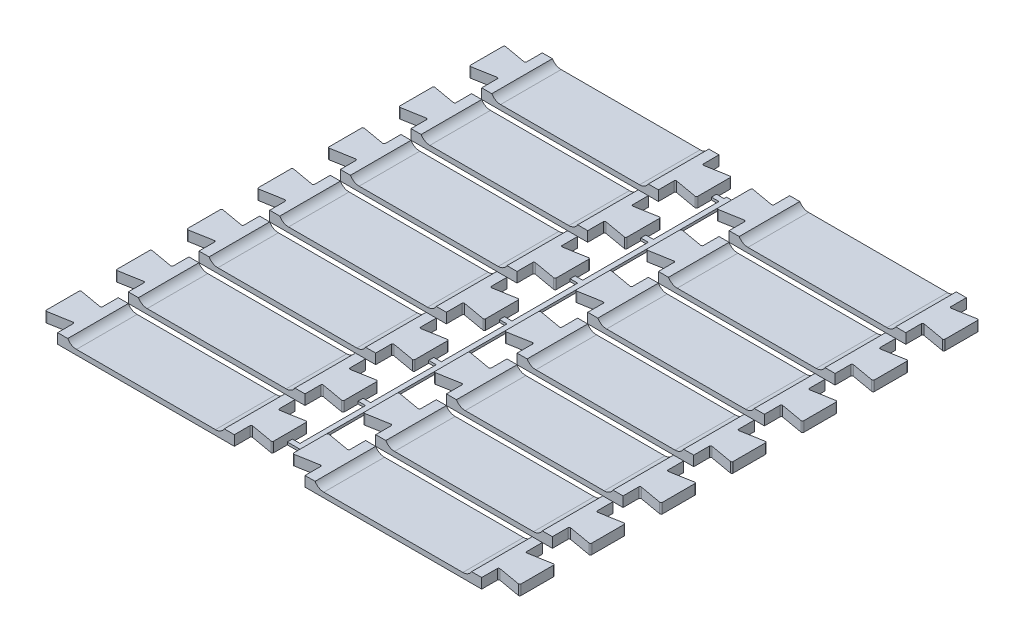
SolidWorks part; units mm, degrees
ref_plane "Front Plane" through (0, 0, 0) normal (0, 0, 1) x (1, 0, 0)
ref_plane "Top Plane" through (0, 0, 0) normal (0, 1, 0) x (1, 0, 0)
ref_plane "Right Plane" through (0, 0, 0) normal (1, 0, 0) x (0, 0, -1)
sketch "Sketch1" plane through (0, 0, 0) normal (0, 1, 0) x (1, 0, 0)
  line L0 (-17.5, 2.6184) -> (-22.5, 3.5)
  line L1 (-17.5, -6) -> (17.5, -6)
  line L2 (-17.5, -6) -> (-17.5, -2.6184)
  line L3 (-17.5, 6) -> (17.5, 6)
  line L4 (17.5, -6) -> (17.5, -2.6184)
  line L5 (-17.5, -6) -> (17.5, 6) construction
  line L6 (-17.5, 6) -> (17.5, -6) construction
  line L7 (-22.5, 3.5) -> (-22.5, -3.5)
  line L8 (-10, 0) -> (-18.3718, 0) construction
  line L9 (-17.5, -2.6184) -> (-22.5, -3.5)
  line L10 (-17.5, 2.6184) -> (-17.5, 6)
  line L11 (0, 0) -> (0, 6) construction
  line L12 (17.5, -2.6184) -> (22.5, -3.5)
  line L13 (22.5, 3.5) -> (22.5, -3.5)
  line L14 (17.5, 2.6184) -> (22.5, 3.5)
  line L15 (17.5, 2.6184) -> (17.5, 6)
  line L16 (-17.5, 6) -> (-27.9194, 6) construction
  point P0 (0, 0)
  point P13 (-22.5, 0)
  dimension "D1" = 12
  dimension "D2" = 35
  dimension "D3" = 3.5
  dimension "D4" = 80
  dimension "D5" = 5
extrude "Boss-Extrude1" add sketch "Sketch1" along normal blind 2
fillet "Fillet1" radius 0.25 8 edges at (-17.5, 1, 2.6184) (-22.5, 1, 3.5) (-22.5, 1, -3.5) (-17.5, 1, -2.6184) (17.5, 1, -2.6184) (22.5, 1, -3.5) (22.5, 1, 3.5) (17.5, 1, 2.6184)
shell "Shell1" [suppressed] thickness 1
fillet "Fillet2" [suppressed] radius 0.5
fillet "Fillet5" [suppressed] radius 1.5
sketch "Sketch2" plane through (0, 0, 0) normal (0, 0, 1) x (1, 0, 0)
  line L0 (-17.5, 2) -> (17.5, 2) construction
  line L1 (0, 0) -> (0, 2) construction
  line L2 (-14.5, 2) -> (-14.5, 5.1779)
  line L3 (-17.5, 0) -> (17.5, 0) construction
  line L4 (-14.5, 5.1779) -> (14.5, 5.1779)
  line L5 (14.5, 2) -> (14.5, 5.1779)
  spline S0 degree 3 poles (-14.5, 2) (-10.1117, 3.708) (-5.6899, 1.0248) (0, 1) knots 0 0 0 0 1 1 1 1
  spline S1 degree 3 poles (14.5, 2) (10.1117, 3.708) (5.6899, 1.0248) (0, 1) knots 0 0 0 0 1 1 1 1
  point P15 (0, 5.1779)
  dimension "D1" = 14.5
  dimension "D2" = 10
  dimension "D3" = 1
extrude "Cut-Extrude1" [suppressed] cut sketch "Sketch2" against normal mid plane 12
sketch "Sketch3" plane through (0, 2, 0) normal (0, 1, 0) x (1, 0, 0)
  line L0 (17.5, 6) -> (-17.5, 6) construction
  line L1 (-15.5, 6) -> (15.5, 6)
  line L2 (-15.5, 6) -> (-15.5, -6)
  line L3 (-15.5, -6) -> (15.5, -6)
  line L4 (15.5, 6) -> (15.5, -6)
  line L5 (-17.5, -6) -> (17.5, -6) construction
  line L6 (-17.5, 6) -> (-17.5, 2.9163) construction
  line L7 (17.5, 2.9163) -> (17.5, 6) construction
  point P8 (-17.5, 4.4582)
  point P11 (17.5, 4.4582)
  dimension "D1" = 2
  dimension "D2" = 2
extrude "Cut-Extrude2" cut sketch "Sketch3" against normal blind 1
fillet "Fillet6" radius 2 2 edges at (-15.5, 1, 0) (15.5, 1, 0)
sketch "Sketch4" plane through (0, 0, 0) normal (0, 1, 0) x (1, 0, 0)
  line L1 (-29.6701, -11.4809) -> (80.3299, -11.4809)
  line L2 (-29.6701, -11.4809) -> (-29.6701, 78.5191)
  line L3 (-29.6701, 78.5191) -> (80.3299, 78.5191)
  line L4 (80.3299, -11.4809) -> (80.3299, 78.5191)
  line L5 (21.5, 0.5) -> (24.5, 0.5)
  line L6 (21.5, 0.5) -> (21.5, -0.5)
  line L7 (21.5, -0.5) -> (24.5, -0.5)
  line L8 (24.5, 0.5) -> (24.5, -0.5)
  dimension "D1" = 90
  dimension "D2" = 110
  dimension "D3" = 3
  dimension "D4" = 21.5
  dimension "D5" = 0.5
  dimension "D6" = 1
extrude "Boss-Extrude2" add sketch "Sketch4" along normal blind 0.5 contours L7 L8 L5 L6
ref_plane "Plane1" through (24.5, 0, 0) normal (1, 0, 0) x (0, 0, -1)
mirror "Mirror1" about plane through (24.5, 0, 0) normal (1, 0, 0) of bodies 104
sketch "Sketch6" plane through (0, 0, 0) normal (0, 1, 0) x (1, 0, 0)
  line L0 (24.5, 0) -> (24.5, 45.0914) construction
  line L1 (24.5, -55) -> (24.5, 55) construction
pattern_linear "LPattern1" count 7 spacing 14 along (0, 0, -1) of bodies 105
sketch "Sketch5" plane through (0, 0, 0) normal (0, 1, 0) x (1, 0, 0)
  line L0 (22.5, -0.5) -> (22.5, 0.5) construction
  line L1 (24, 0) -> (25, 0)
  line L2 (24, 0) -> (24, 85)
  line L3 (24, 85) -> (25, 85)
  line L4 (25, 0) -> (25, 85)
  line L5 (22.5, -0.5) -> (26.5, -0.5) construction
  dimension "D1" = 1.5
  dimension "D2" = 1
  dimension "D3" = 0.5
  dimension "D4" = 85
extrude "Boss-Extrude3" add sketch "Sketch5" along normal blind 0.5
combine bodies "Combine1" operation type add bodies to combine 106 107 108 109 110 111 112
